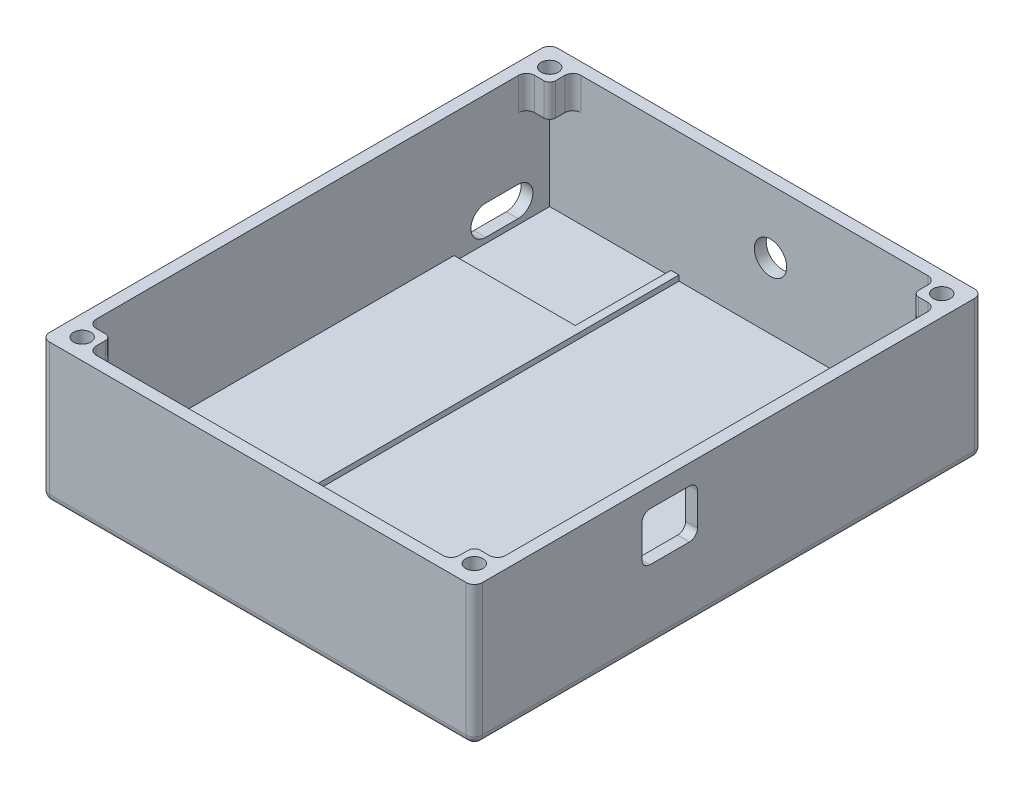
SolidWorks part; units mm, degrees
ref_plane "Front Plane" through (0, 0, 0) normal (0, 0, 1) x (1, 0, 0)
ref_plane "Top Plane" through (0, 0, 0) normal (0, 1, 0) x (1, 0, 0)
ref_plane "Right Plane" through (0, 0, 0) normal (1, 0, 0) x (0, 0, -1)
sketch "Sketch1" plane through (0, 0, 0) normal (0, 1, 0) x (1, 0, 0)
  line L0 (38, -26.85) -> (-38, -26.85)
  line L1 (-38, -45) -> (38, -45)
  line L2 (-38, -45) -> (-38, 45)
  line L3 (-38, 45) -> (38, 45)
  line L4 (38, -45) -> (38, 45)
  line L5 (-38, -45) -> (38, 45) construction
  line L6 (-38, 45) -> (38, -45) construction
  line L7 (-40.2, -47.2) -> (40.2, -47.2)
  line L8 (-40.2, -47.2) -> (-40.2, 47.2)
  line L9 (-40.2, 47.2) -> (40.2, 47.2)
  line L10 (40.2, -47.2) -> (40.2, 47.2)
  line L11 (-40.2, -47.2) -> (40.2, 47.2) construction
  line L12 (-40.2, 47.2) -> (40.2, -47.2) construction
  line L13 (-14, -26.85) -> (-14, 45)
  line L14 (-38, 27.25) -> (-15.5, 27.25)
  line L15 (-15.5, 27.25) -> (-15.5, 45)
  point P0 (0, 0)
  point P6 (0, 0)
  dimension "D1" = 76
  dimension "D2" = 90
  dimension "D3" = 2.2
  dimension "D4" = 2.2
  dimension "D5" = 18.15
  dimension "D6" = 52
  dimension "D7" = 17.75
  dimension "D8" = 22.5
extrude "Boss-Extrude1" add sketch "Sketch1" along normal blind 2 contours L15 L14 L2 L0 L13 L3 | L14 L15 L3 L2 | L13 L0 L4 L3 | L1 L4 L0 L2 region at (0, 0, 35.925) region at (12, 0, -9.075) region at (-25.7739, 0, -0.9219) region at (-26.75, 0, -36.125)
extrude "Boss-Extrude2" add sketch "Sketch1<3>" along normal blind 3 contours L15 L14 L2 L0 L13 L3 region at (-25.7739, 0, -0.9219)
sketch "Sketch1<3>" plane through (0, 0, 0) normal (0, 1, 0) x (1, 0, 0) same geometry as "Sketch1"
extrude "Boss-Extrude3" add sketch "Sketch1<4>" along normal blind 26 contours L7 L10 L9 L8 L4 L1 L2 L3 region at (-38.96, 0, 0)
sketch "Sketch1<4>" plane through (0, 0, 0) normal (0, 1, 0) x (1, 0, 0) same geometry as "Sketch1"
sketch "Sketch2" plane through (-40.2, 0, 0) normal (-1, 0, 0) x (0, 0, 1)
  line L0 (47.2, 26) -> (47.2, 0) construction
  line L1 (47.2, 0) -> (-47.2, 0) construction
  line L2 (26.9643, 5.5) -> (26.9643, 0)
  line L4 (41.905, 0) -> (26.9643, 0)
  line L5 (26.9643, 5.5) -> (28.7643, 5.5)
  line L6 (43.1147, 5.5375) -> (45, 5.5375)
  line L7 (45, 5.5375) -> (47.2, 5.5375)
  line L8 (47.2, 5.5375) -> (47.2, 0)
  line L9 (47.2, 0) -> (41.905, 0)
  line L13 (16.0643, 13.3) -> (5.7643, 13.3)
  line L14 (16.0643, 13.3) -> (16.0643, 22.3)
  line L15 (16.0643, 22.3) -> (5.7643, 22.3)
  line L16 (5.7643, 13.3) -> (5.7643, 22.3)
  line L17 (16.0643, 13.3) -> (5.7643, 22.3) construction
  line L18 (16.0643, 22.3) -> (5.7643, 13.3) construction
  arc A0 (28.7643, 5.5) -> (43.1147, 5.5375) centre (35.925, 11.075) ccw
  point P6 (2.9558, 17.8)
  point P14 (26.9643, 2.75)
  point P18 (10.9143, 17.8)
  line M1 (-47.2, 0) -> (47.2, 0)
  line M2 (47.2, 0) -> (47.2, 26)
  dimension "D3" = 18.15
  dimension "D1" = 11.275
  dimension "D2" = 11.075
  dimension "D4" = 5.5
  dimension "D5" = 1.8853
  dimension "D6" = 1.8
  dimension "D7" = 2.2
  dimension "D8" = 10.3
  dimension "D9" = 9
  dimension "D10" = 13.3
  dimension "D11" = 10.9
extrude "Boss-Extrude4" add sketch "Sketch2" against normal up to surface (78.2 mm away) contours A0 L5 L2 L7 L6 M1 M2 region at (-40.2, 2.1504, 37.6273) up to face at (38, 14, 0)
extrude "Cut-Extrude1" cut sketch "Sketch2<3>" against normal blind 26 from surface contours L16 L13 L14 L15 region at (-40.2, 17.8, 10.9143) starting at face at (38, 9.3195, 15.7271)
sketch "Sketch2<3>" plane through (-40.2, 0, 0) normal (-1, 0, 0) x (0, 0, 1) same geometry as "Sketch2"
sketch "Sketch3" plane through (-40.2, 0, 0) normal (-1, 0, 0) x (0, 0, 1)
  line L0 (-39.125, 5.75) -> (-33.125, 5.75) construction
  line L1 (-39.125, 8.5) -> (-33.125, 8.5)
  line L2 (-39.125, 3) -> (-33.125, 3)
  line L3 (-47.2, 26) -> (-47.2, 0) construction
  line L4 (47.2, 0) -> (-47.2, 0) construction
  arc A0 (-39.125, 8.5) -> (-39.125, 3) centre (-39.125, 5.75) ccw
  arc A1 (-33.125, 3) -> (-33.125, 8.5) centre (-33.125, 5.75) ccw
  point P2 (-36.125, 5.75)
  dimension "D3" = 6
  dimension "D1" = 11.075
  dimension "D2" = 5.5
  dimension "D4" = 3
extrude "Cut-Extrude2" cut sketch "Sketch3" against normal blind 26
fillet "Fillet1" radius 1.5 12 edges at (-40.2, 0, 0) (0, 0, -47.2) (40.2, 0, 0) (0, 0, 47.2) (-40.2, 13, 47.2) (-40.2, 13, -47.2) (40.2, 13, -47.2) (40.2, 13, 47.2) (39.1, 13.3, 16.0643) (39.1, 13.3, 5.7643) (39.1, 22.3, 5.7643) (39.1, 22.3, 16.0643)
sketch "Sketch4" plane through (0, 0, -47.2) normal (0, 0, -1) x (-1, 0, 0)
  line L0 (40.2, 26) -> (40.2, 1.5) construction
  line L1 (38.7, 0) -> (-38.7, 0) construction
  circle A0 centre (-3, 14.2624) radius 3
  dimension "D3" = 6
  dimension "D1" = 43.2
  dimension "D2" = 14.2624
extrude "Cut-Extrude3" cut sketch "Sketch4" against normal blind 26
sketch "Sketch5" plane through (0, 26, 0) normal (0, 1, 0) x (1, 0, 0)
  line L0 (-33.7, 45) -> (-33.7, 41.8)
  line L1 (-38, 45) -> (-15.5, 45) construction
  line L2 (-34.8, 40.7) -> (-38, 40.7)
  line L3 (-38, -45) -> (-38, 45) construction
  line L5 (0, 59.375) -> (0, -65.6409) construction
  line L6 (-53.0411, 0) -> (66.7309, 0) construction
  line L7 (-38, 40.7) -> (-39.1, 40.7)
  line L8 (-39.1, 40.7) -> (-39.1, 46.1)
  line L9 (-39.1, 46.1) -> (-33.7, 46.1)
  line L10 (-33.7, 46.1) -> (-33.7, 45)
  line L11 (33.7, 46.1) -> (33.7, 45)
  line L12 (39.1, 46.1) -> (33.7, 46.1)
  line L13 (39.1, 40.7) -> (39.1, 46.1)
  line L14 (38, 40.7) -> (39.1, 40.7)
  line L15 (34.8, 40.7) -> (38, 40.7)
  line L16 (33.7, 45) -> (33.7, 41.8)
  line L17 (33.7, -45) -> (33.7, -41.8)
  line L18 (34.8, -40.7) -> (38, -40.7)
  line L19 (38, -40.7) -> (39.1, -40.7)
  line L20 (39.1, -40.7) -> (39.1, -46.1)
  line L21 (39.1, -46.1) -> (33.7, -46.1)
  line L22 (33.7, -46.1) -> (33.7, -45)
  line L23 (-33.7, -46.1) -> (-33.7, -45)
  line L24 (-39.1, -46.1) -> (-33.7, -46.1)
  line L25 (-39.1, -40.7) -> (-39.1, -46.1)
  line L26 (-38, -40.7) -> (-39.1, -40.7)
  line L27 (-34.8, -40.7) -> (-38, -40.7)
  line L28 (-33.7, -45) -> (-33.7, -41.8)
  circle A0 centre (-36.4, 43.4) radius 1.6
  arc A1 (-34.8, 40.7) -> (-33.7, 41.8) centre (-34.8, 41.8) ccw
  arc A2 (34.8, 40.7) -> (33.7, 41.8) centre (34.8, 41.8) cw
  circle A3 centre (36.4, 43.4) radius 1.6
  circle A4 centre (36.4, -43.4) radius 1.6
  arc A5 (34.8, -40.7) -> (33.7, -41.8) centre (34.8, -41.8) ccw
  arc A6 (-34.8, -40.7) -> (-33.7, -41.8) centre (-34.8, -41.8) cw
  circle A7 centre (-36.4, -43.4) radius 1.6
  dimension "D1" = 3.2
  dimension "D2" = 2.7
  dimension "D3" = 2.7
  dimension "D4" = 1.1
  dimension "D5" = 5.4
  dimension "D6" = 5.4
extrude "Boss-Extrude5" add sketch "Sketch5" against normal blind 6
fillet "Fillet2" radius 1.5 8 edges at (-38, 23, 40.7) (-33.7, 23, 45) (33.7, 23, 45) (38, 23, 40.7) (38, 23, -40.7) (33.7, 23, -45) (-38, 23, -40.7) (-33.7, 23, -45)
